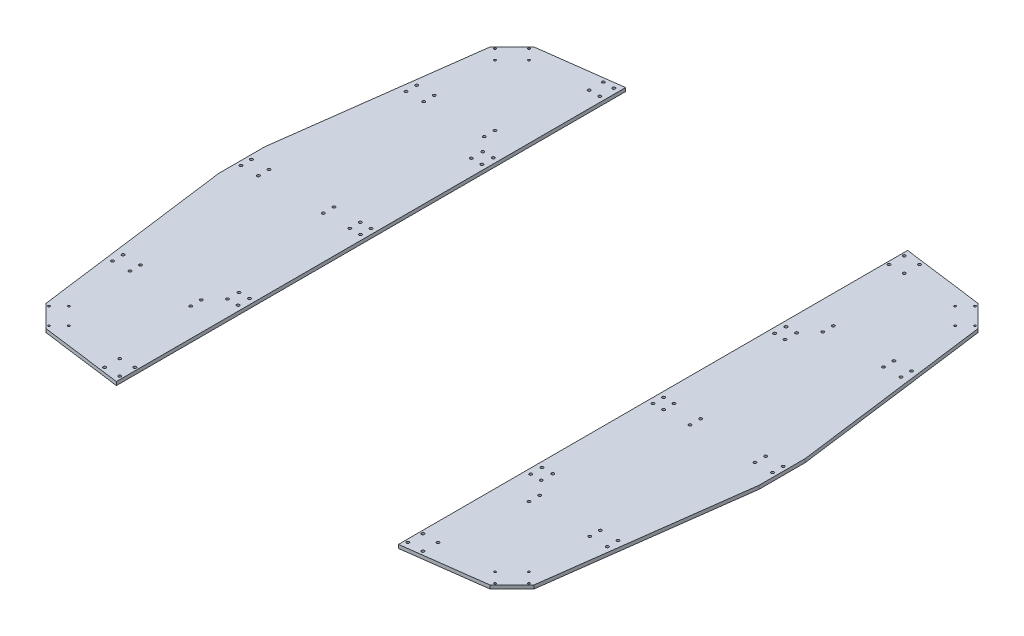
SolidWorks part; units mm, degrees
ref_plane "前视基准面" through (0, 0, 0) normal (0, 0, 1) x (1, 0, 0)
ref_plane "上视基准面" through (0, 0, 0) normal (0, 1, 0) x (1, 0, 0)
ref_plane "右视基准面" through (0, 0, 0) normal (1, 0, 0) x (0, 0, -1)
other "Configuration Table"
sketch "草图1" plane through (0, 0, 0) normal (0, 1, 0) x (1, 0, 0)
  line L0 (-314.9222, 345.9222) -> (-345.9222, 314.9222)
  line L5 (325, -325) -> (-325, 325) construction
  line L6 (325, 325) -> (-325, -325) construction
  line L7 (0, 325) -> (0, -325) construction
  line L8 (-383.07, 0) -> (383.0748, 0) construction
  line L9 (314.9222, 345.9222) -> (32.7201, 383.0748)
  line L10 (314.9222, 345.9222) -> (345.9222, 314.9222)
  line L11 (-383.07, 13.0001) -> (-230, 13.0001) construction
  line L12 (-314.9222, 345.9222) -> (-32.7201, 383.0748)
  line L13 (0, 325) -> (0, 399.6983)
  line L14 (-32.7201, 383.0748) -> (32.7201, 383.0748)
  line L15 (314.9222, -345.9222) -> (32.7201, -383.0748)
  line L16 (-32.7201, -383.0748) -> (32.7201, -383.0748)
  line L17 (-314.9222, -345.9222) -> (-32.7201, -383.0748)
  line L18 (-314.9222, -345.9222) -> (-345.9222, -314.9222)
  line L19 (-345.9222, 314.9222) -> (-383.0748, 32.7201)
  line L20 (-383.0748, -32.7201) -> (-383.0748, 32.7201)
  line L21 (-345.9222, -314.9222) -> (-383.0748, -32.7201)
  line L22 (-345.9222, -314.9222) -> (-314.9222, -345.9222)
  line L23 (345.9222, -314.9222) -> (314.9222, -345.9222)
  line L24 (345.9222, -314.9222) -> (383.0748, -32.7201)
  line L25 (383.0748, 32.7201) -> (383.0748, -32.7201)
  line L26 (345.9222, 314.9222) -> (383.0748, 32.7201)
  line L27 (-383.07, -12.9999) -> (-230, -12.9999) construction
  line L29 (361.6863, 195.182) -> (230, 195.182) construction
  line L30 (358.2633, 221.182) -> (230, 221.182) construction
  line L31 (-358.2633, 221.182) -> (-230, 221.182) construction
  line L32 (-361.6863, 195.182) -> (-230, 195.182) construction
  line L33 (361.6863, -195.182) -> (230, -195.182) construction
  line L34 (358.2633, -221.182) -> (230, -221.182) construction
  line L35 (-361.6863, -195.182) -> (-230, -195.182) construction
  line L36 (-358.2633, -221.182) -> (-230, -221.182) construction
  line L37 (-228, -357.3657) -> (-228, 357.3618) construction
  line L38 (-202, -360.7887) -> (-202, 360.7847) construction
  line L39 (383.07, 13.0001) -> (230, 13.0001) construction
  circle A5 centre (0, 0) radius 250
  circle A6 centre (302.1379, 326.1795) radius 1.5
  circle A7 centre (316.28, 340.3217) radius 1.5
  circle A8 centre (340.3217, 316.28) radius 1.5
  circle A9 centre (326.1795, 302.1379) radius 1.5
  circle A10 centre (302.1379, -326.1795) radius 1.5
  circle A11 centre (316.28, -340.3217) radius 1.5
  circle A12 centre (326.1795, -302.1379) radius 1.5
  circle A13 centre (340.3217, -316.28) radius 1.5
  circle A14 centre (-326.1795, -302.1379) radius 1.5
  circle A15 centre (-340.3217, -316.28) radius 1.5
  circle A16 centre (-302.1379, -326.1795) radius 1.5
  circle A17 centre (-316.28, -340.3217) radius 1.5
  circle A18 centre (-302.1379, 326.1795) radius 1.5
  circle A19 centre (-316.28, 340.3217) radius 1.5
  circle A20 centre (-326.1795, 302.1379) radius 1.5
  circle A21 centre (-340.3217, 316.28) radius 1.5
  circle A22 centre (350.9184, 215.682) radius 2
  circle A23 centre (377.0748, 7.5001) radius 2
  circle A24 centre (350.9184, 200.682) radius 2
  circle A25 centre (325.9184, 215.682) radius 2
  circle A26 centre (325.9184, 200.682) radius 2
  circle A27 centre (377.0748, -7.5951) radius 2
  circle A28 centre (352.0748, 7.5001) radius 2
  circle A29 centre (352.0748, -7.5951) radius 2
  circle A30 centre (350.9184, -200.682) radius 2
  circle A31 centre (350.9184, -215.682) radius 2
  circle A32 centre (325.9184, -200.682) radius 2
  circle A33 centre (325.9184, -215.682) radius 2
  circle A34 centre (-350.9184, -200.682) radius 2
  circle A35 centre (-325.9184, -200.682) radius 2
  circle A36 centre (-350.9184, -215.682) radius 2
  circle A37 centre (-325.9184, -215.682) radius 2
  circle A38 centre (-377.0748, 7.5001) radius 2
  circle A39 centre (-352.0748, 7.5001) radius 2
  circle A40 centre (-377.0748, -7.4999) radius 2
  circle A41 centre (-352.0748, -7.4999) radius 2
  circle A42 centre (-350.9184, 215.682) radius 2
  circle A43 centre (-350.9184, 200.682) radius 2
  circle A44 centre (-325.9184, 215.682) radius 2
  circle A45 centre (-325.9184, 200.682) radius 2
  circle A46 centre (-222.5, -164.8255) radius 2
  circle A47 centre (-207.5, -164.8255) radius 2
  circle A48 centre (-222.5, -181.0301) radius 2
  circle A49 centre (-207.5, -181.0301) radius 2
  circle A50 centre (-222.5, 181.0301) radius 2
  circle A51 centre (-207.5, 164.8255) radius 2
  circle A52 centre (-222.5, 164.8255) radius 2
  circle A53 centre (-207.5, 181.0301) radius 2
  circle A54 centre (207.5, -164.8255) radius 2
  circle A55 centre (222.5, -164.8255) radius 2
  circle A56 centre (207.5, -181.0301) radius 2
  circle A57 centre (222.5, -181.0301) radius 2
  circle A58 centre (207.5, 164.8255) radius 2
  circle A59 centre (222.5, 164.8255) radius 2
  circle A60 centre (207.5, 181.0301) radius 2
  circle A61 centre (222.5, 181.0301) radius 2
  circle A62 centre (-240, 215.682) radius 2
  circle A63 centre (-240, 200.682) radius 2
  circle A64 centre (-260, 7.5) radius 2
  circle A65 centre (-260, -7.5) radius 2
  circle A66 centre (-240, -200.682) radius 2
  circle A67 centre (-240, -215.682) radius 2
  circle A68 centre (240, -215.682) radius 2
  circle A69 centre (240, -200.682) radius 2
  circle A72 centre (240, 200.682) radius 2
  circle A73 centre (240, 215.682) radius 2
  circle A74 centre (207.5, 9.4052) radius 2
  circle A75 centre (222.5, 9.4052) radius 2
  circle A76 centre (207.5, -5.5948) radius 2
  circle A77 centre (222.5, -5.5948) radius 2
  circle A78 centre (-222.5, -5.5948) radius 2
  circle A79 centre (-207.5, -5.5948) radius 2
  circle A80 centre (-222.5, 9.4052) radius 2
  circle A81 centre (-207.5, 9.4052) radius 2
  circle A82 centre (260, -7.5) radius 2
  circle A83 centre (260, 7.5) radius 2
  point P0 (0, 0)
  point P13 (0, 383.0748)
  point P24 (-330.4222, -330.4222)
  point P75 (0, 0)
  dimension "D6" = 25
  dimension "D7" = 15
  dimension "D8" = 500
  dimension "D5" = 4
  dimension "D13" = 6
  dimension "D14" = 6
  dimension "D15" = 6
  dimension "D16" = 6
  dimension "D17" = 25
  dimension "D20" = 8
  dimension "D21" = 25
  dimension "D23" = 8
  dimension "D28" = 5.5
  dimension "D29" = 5.5
  dimension "D30" = 5.5
  dimension "D31" = 5.5
  dimension "D32" = 5.5
  dimension "D33" = 5.5
  dimension "D35" = 5.5
  dimension "D37" = 5.5
  dimension "D1" = 650
  dimension "D2" = 650
  dimension "D3" = 31
  dimension "D4" = 142.5
  dimension "D9" = 5.5
  dimension "D10" = 5.5
  dimension "D11" = 25
  dimension "D12" = 25
  dimension "D22" = 25
  dimension "D24" = 25
  dimension "D25" = 25
  dimension "D26" = 25
  dimension "D27" = 5.5
  dimension "D34" = 5.5
  dimension "D36" = 5.5
  dimension "D38" = 7.5001
  dimension "D39" = 7.4999
  dimension "D40" = 7.5
  dimension "D41" = 7.5
extrude "凸台-拉伸2" add sketch "草图1" along normal blind 5 contours L26 L10 L9 L14 L12 L0 L19 L20 L21 L18 L17 L16 L15 L23 L24 L25 | A13 L22 | L22 | A13 L18 region at (-172.4069, 0, -353.7562)
sketch "草图2" plane through (0, 5, 0) normal (0, 1, 0) x (1, 0, 0)
  line L0 (0, 0) -> (-330.4222, -330.4222) construction
  line L1 (0, 383.0748) -> (0, -383.0748)
  line L2 (-32.7201, 383.0748) -> (32.7201, 383.0748) construction
  line L3 (-32.7201, -383.0748) -> (32.7201, -383.0748) construction
  line L4 (-200, 361.052) -> (-200, -361.052)
  line L5 (-314.9222, 345.9222) -> (-32.7201, 383.0748) construction
  line L6 (-314.9222, -345.9222) -> (-32.7201, -383.0748) construction
  line L7 (200, 361.052) -> (200, -361.052)
  line L8 (314.9222, 345.9222) -> (32.7201, 383.0748) construction
  line L9 (314.9222, -345.9222) -> (32.7201, -383.0748) construction
  line L10 (-200, 361.052) -> (-200, 484.7149)
  line L11 (-200, 484.7149) -> (200, 484.7149)
  line L12 (200, 484.7149) -> (200, 361.052)
  line L13 (-200, -361.052) -> (-200, -418.819)
  line L14 (-200, -418.819) -> (200, -418.819)
  line L15 (200, -418.819) -> (200, -361.052)
  dimension "D1" = 200
  dimension "D2" = 200
extrude "切除-拉伸1" cut sketch "草图2" against normal blind 122 and the other way through all contours L4 L1 | L7 L1 | L7 L1 | L4 L1 | L0 L4 region at (-190.1188, 5, -422.8834)
sketch "草图3" plane through (0, 0, 0) normal (0, -1, 0) x (-1, 0, 0)
  circle A0 centre (225.7527, -352.0225) radius 2
  circle A1 centre (204.2473, -352.0225) radius 2
  circle A2 centre (225.7527, -330.517) radius 2
  circle A3 centre (204.2473, -330.517) radius 2
extrude "切除-拉伸2" cut sketch "草图3" along normal through all and the other way blind 39 contours A0 | A1 | A2 | A3
sketch "草图4" plane through (0, 5, 0) normal (0, 1, 0) x (1, 0, 0)
  line L0 (-222.5, 352.0186) -> (-207.5, 352.0186)
  line L1 (-215, 352.0186) -> (-215, 337.3883)
  line L2 (-228, -357.3657) -> (-228, 357.3618) construction
  line L3 (-202, -360.7887) -> (-202, 360.7847) construction
  line L4 (-228, -357.3657) -> (-228, 357.3618)
  line L5 (-202, -360.7887) -> (-202, 360.7847)
  line L6 (-202, 337.3883) -> (-228, 337.3883)
  circle A0 centre (-222.5, 352.0186) radius 2
  circle A1 centre (-207.5, 352.0186) radius 2
  circle A2 centre (-222.5, 332.0186) radius 2
  circle A3 centre (-207.5, 332.0186) radius 2
  circle A4 centre (204.2473, 330.5131) radius 2
  circle A5 centre (225.7527, 330.5131) radius 2
  circle A6 centre (204.2473, 352.0186) radius 2
  circle A7 centre (225.7527, 352.0186) radius 2
  circle A8 centre (204.2473, -352.0225) radius 2
  circle A9 centre (225.7527, -352.0225) radius 2
  circle A10 centre (204.2473, -330.517) radius 2
  circle A11 centre (225.7527, -330.517) radius 2
  point P3 (-215, 337.3883)
  point P19 (0, 0)
  point P20 (0, 0)
  point P21 (0, 0)
  point P24 (0, 0)
  dimension "D1" = 4
  dimension "D2" = 15
  dimension "D3" = 20
extrude "切除-拉伸3" cut sketch "草图4" against normal through all and the other way blind 20 contours A8 | A9 | A11 | A4 | A6 | A5 | A7 | A1 | A0 | A2 | A3 | A10 region at (-207.5, 5, -353.962) region at (-224.4434, 5, -352.0186) region at (-222.5, 5, -332.0186) region at (-207.5, 5, -332.0186) region at (204.2473, 5, -330.5131) region at (225.7527, 5, -330.5131) region at (204.2473, 5, -352.0186) region at (225.7527, 5, -352.0186) region at (204.2473, 5, 352.0225) region at (225.7527, 5, 352.0225) region at (225.7527, 5, 330.517)
sketch "草图5" plane through (0, 5, 0) normal (0, 1, 0) x (1, 0, 0)
  line L0 (-200, 150) -> (-200, -150)
  line L1 (200, 150) -> (200, -150)
  line L2 (-260, 7.5) -> (-260, -7.5) construction
  line L3 (-260, -7.5) -> (-200, -7.5) construction
  line L4 (-200, -7.5) -> (-200, 7.5)
  line L5 (-200, 7.5) -> (-260, 7.5) construction
  line L6 (-228, -357.3657) -> (-228, 357.3618) construction
  line L7 (-202, -360.7887) -> (-202, 360.7847) construction
  line L8 (0, 250) -> (0, -250) construction
  line L9 (-200, 361.048) -> (-200, -361.052) construction
  circle A0 centre (0, 0) radius 250
  circle A1 centre (-222.5, 7.5) radius 2
  circle A2 centre (-207.5, 7.5) radius 2
  circle A3 centre (-222.5, -7.5) radius 2
  circle A4 centre (-207.5, -7.5) radius 2
  circle A5 centre (207.5, -7.5) radius 2
  circle A6 centre (222.5, -7.5) radius 2
  circle A7 centre (207.5, 7.5) radius 2
  circle A8 centre (222.5, 7.5) radius 2
  dimension "D1" = 5.5
  dimension "D2" = 5.5
  dimension "D3" = 5.5
  dimension "D4" = 5.5
extrude "凸台-拉伸3" add sketch "草图5" against normal blind 5 contours L0 | L1 A0 region at (-220.2076, 5, 0) region at (220.2076, 5, 0)
